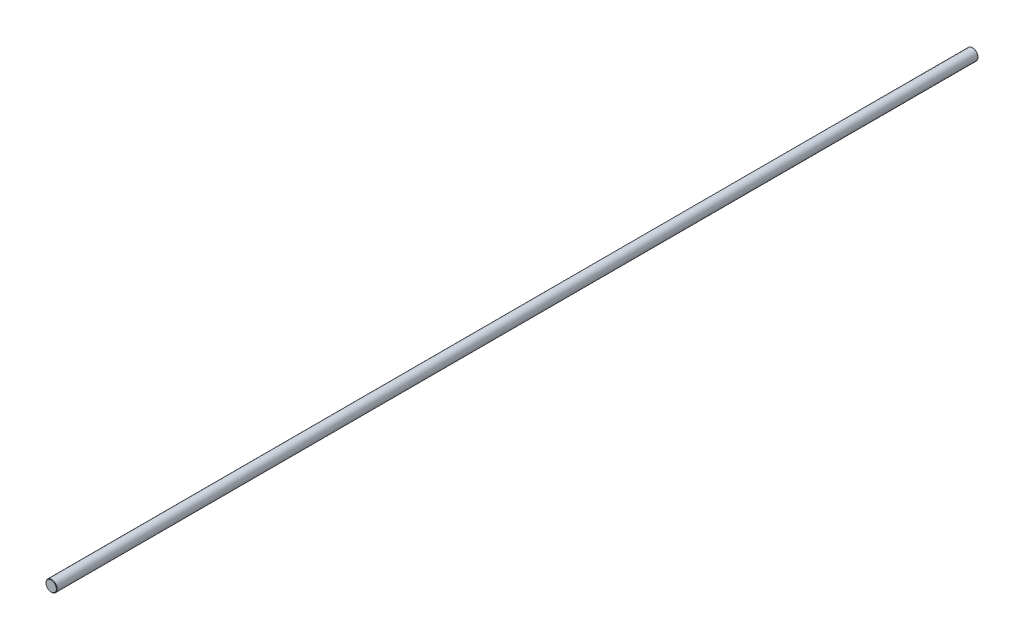
SolidWorks part; units mm, degrees
material "AISI 304"
ref_plane "Спереди" through (0, 0, 0) normal (0, 0, 1) x (1, 0, 0)
ref_plane "Сверху" through (0, 0, 0) normal (0, 1, 0) x (1, 0, 0)
ref_plane "Справа" through (0, 0, 0) normal (1, 0, 0) x (0, 0, -1)
ref_axis "ОсьX" through (-88.99, 0, 0) along (1, 0, 0)
ref_axis "ОсьZ" through (0, 55, 0) along (0, -1, 0)
ref_axis "ОсьY" through (0, 0, -88.99) along (0, 0, 1)
sketch "Эскиз1" plane through (0, 0, 0) normal (0, 0, 1) x (1, 0, 0)
  circle A0 centre (0, 0) radius 12.5
  dimension "D1" = 25
extrude "Бобышка-Вытянуть1" add sketch "Эскиз1" along normal mid plane 2054
chamfer "Фаска1" distance 1 angle 45 2 edges at (12.5, 0, -1027) (12.5, 0, 1027)
